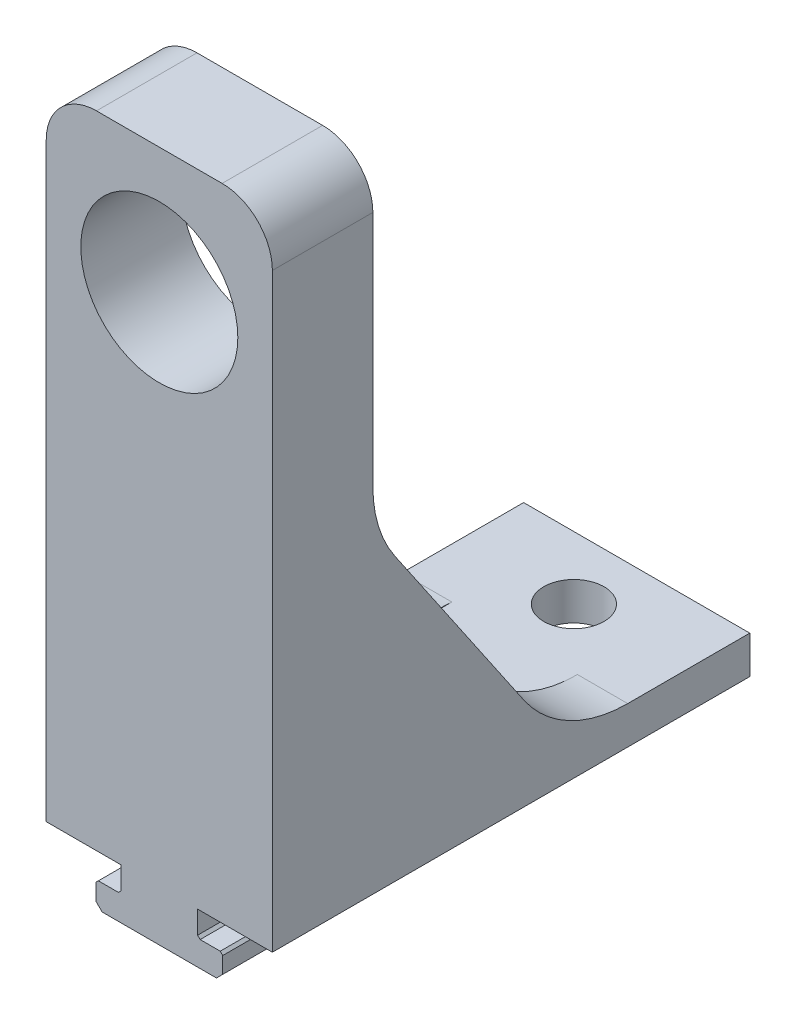
SolidWorks part; units mm, degrees
ref_plane "前视基准面" through (0, 0, 0) normal (0, 0, 1) x (1, 0, 0)
ref_plane "上视基准面" through (0, 0, 0) normal (0, 1, 0) x (1, 0, 0)
ref_plane "右视基准面" through (0, 0, 0) normal (1, 0, 0) x (0, 0, -1)
sketch "草图1" plane through (0, 0, 0) normal (0, 0, 1) x (1, 0, 0)
  line L0 (0, -1000) -> (0, 49000) construction
  line L1 (-3.2, 10) -> (-3.2, 8.5) construction
  line L2 (-10, -10) -> (10, -10) construction
  line L3 (-10, -10) -> (-10, 10) construction
  line L4 (-10, 10) -> (10, 10) construction
  line L5 (-1000, 0) -> (49000, 0) construction
  line L6 (10, -10) -> (10, 10) construction
  line L7 (-10, -10) -> (10, 10) construction
  line L8 (-10, 10) -> (10, -10) construction
  line L9 (-3.2, 8.5) -> (-5.5, 8.5) construction
  line L10 (-5.5, 8.5) -> (-5.5, 6.7) construction
  line L11 (-5.5, 6.7) -> (-2.8, 4) construction
  line L12 (-2.8, 4) -> (2.8, 4) construction
  line L13 (5.5, 6.7) -> (2.8, 4) construction
  line L14 (5.5, 8.5) -> (5.5, 6.7) construction
  line L15 (3.2, 8.5) -> (5.5, 8.5) construction
  line L16 (3.2, 10) -> (3.2, 8.5) construction
  line L17 (8.5, 3.2) -> (8.5, 5.5) construction
  line L18 (8.5, 5.5) -> (6.7, 5.5) construction
  line L19 (6.7, 5.5) -> (4, 2.8) construction
  line L20 (4, 2.8) -> (4, -2.8) construction
  line L21 (6.7, -5.5) -> (4, -2.8) construction
  line L22 (8.5, -5.5) -> (6.7, -5.5) construction
  line L23 (8.5, -3.2) -> (8.5, -5.5) construction
  line L24 (10, 3.2) -> (8.5, 3.2) construction
  line L25 (10, -3.2) -> (8.5, -3.2) construction
  line L26 (3.2, -8.5) -> (5.5, -8.5) construction
  line L27 (5.5, -8.5) -> (5.5, -6.7) construction
  line L28 (5.5, -6.7) -> (2.8, -4) construction
  line L29 (2.8, -4) -> (-2.8, -4) construction
  line L30 (-5.5, -6.7) -> (-2.8, -4) construction
  line L31 (-5.5, -8.5) -> (-5.5, -6.7) construction
  line L32 (-3.2, -8.5) -> (-5.5, -8.5) construction
  line L33 (3.2, -10) -> (3.2, -8.5) construction
  line L34 (-3.2, -10) -> (-3.2, -8.5) construction
  line L35 (-8.5, -3.2) -> (-8.5, -5.5) construction
  line L36 (-8.5, -5.5) -> (-6.7, -5.5) construction
  line L37 (-6.7, -5.5) -> (-4, -2.8) construction
  line L38 (-4, -2.8) -> (-4, 2.8) construction
  line L39 (-6.7, 5.5) -> (-4, 2.8) construction
  line L40 (-8.5, 5.5) -> (-6.7, 5.5) construction
  line L41 (-8.5, 3.2) -> (-8.5, 5.5) construction
  line L42 (-10, -3.2) -> (-8.5, -3.2) construction
  line L43 (-10, 3.2) -> (-8.5, 3.2) construction
  line L44 (-10, 10) -> (-50, 10) construction
  line L45 (-50, 10) -> (-50, -10) construction
  line L46 (-50, -10) -> (-10, -10) construction
  line L47 (-3.05, 10) -> (-9, 10)
  line L48 (-9, 10) -> (-9, 57)
  line L49 (-5, 61) -> (5, 61)
  line L50 (9, 57) -> (9, 10)
  line L51 (9, 10) -> (3.05, 10)
  line L52 (-9, 13) -> (9, 13)
  line L53 (-3.05, 10) -> (3.05, 10)
  line L68 (-24.55, 6) -> (-15.45, 6) construction
  line L70 (-3.05, 10) -> (-3.05, 8)
  line L71 (-3.05, 8) -> (-5.05, 8)
  line L72 (-5.05, 8) -> (-5.05, 6.5)
  line L73 (-5.05, 6.5) -> (-4.55, 6)
  line L74 (-4.55, 6) -> (4.55, 6)
  line L75 (5.05, 6.5) -> (4.55, 6)
  line L76 (5.05, 8) -> (5.05, 6.5)
  line L77 (3.05, 10) -> (3.05, 8)
  line L78 (3.05, 8) -> (5.05, 8)
  line L79 (-14.95, 6.5) -> (-15.45, 6) construction
  line L80 (-14.95, 8) -> (-14.95, 6.5) construction
  line L81 (-16.95, 8) -> (-14.95, 8) construction
  line L82 (-16.95, 10) -> (-16.95, 8) construction
  line L83 (-23.05, 10) -> (-23.05, 8) construction
  line L84 (-23.05, 8) -> (-25.05, 8) construction
  line L85 (-25.05, 8) -> (-25.05, 6.5) construction
  line L86 (-25.05, 6.5) -> (-24.55, 6) construction
  line L87 (-44.55, 6) -> (-35.45, 6) construction
  line L88 (-34.95, 6.5) -> (-35.45, 6) construction
  line L89 (-34.95, 8) -> (-34.95, 6.5) construction
  line L90 (-36.95, 8) -> (-34.95, 8) construction
  line L91 (-36.95, 10) -> (-36.95, 8) construction
  line L92 (-43.05, 10) -> (-43.05, 8) construction
  line L93 (-43.05, 8) -> (-45.05, 8) construction
  line L94 (-45.05, 8) -> (-45.05, 6.5) construction
  line L95 (-45.05, 6.5) -> (-44.55, 6) construction
  line L96 (-30, 10) -> (-30, -10) construction
  line L97 (-40, 10) -> (-40, -10) construction
  line L98 (-34, 4.55) -> (-34, -4.55) construction
  line L99 (-33.5, -5.05) -> (-34, -4.55) construction
  line L100 (-32, -5.05) -> (-33.5, -5.05) construction
  line L101 (-32, -3.05) -> (-32, -5.05) construction
  line L102 (-32, 3.05) -> (-28, 3.05) construction
  line L103 (-28, -3.05) -> (-32, -3.05) construction
  line L104 (-32, 3.05) -> (-32, 5.05) construction
  line L105 (-32, 5.05) -> (-33.5, 5.05) construction
  line L106 (-33.5, 5.05) -> (-34, 4.55) construction
  line L107 (-35.45, -6) -> (-44.55, -6) construction
  line L108 (-45.05, -6.5) -> (-44.55, -6) construction
  line L109 (-45.05, -8) -> (-45.05, -6.5) construction
  line L110 (-43.05, -8) -> (-45.05, -8) construction
  line L111 (-43.05, -10) -> (-43.05, -8) construction
  line L112 (-36.95, -10) -> (-36.95, -8) construction
  line L113 (-36.95, -8) -> (-34.95, -8) construction
  line L114 (-34.95, -8) -> (-34.95, -6.5) construction
  line L115 (-34.95, -6.5) -> (-35.45, -6) construction
  line L116 (-46, -4.55) -> (-46, 4.55) construction
  line L117 (-46.5, 5.05) -> (-46, 4.55) construction
  line L118 (-48, 5.05) -> (-46.5, 5.05) construction
  line L119 (-48, 3.05) -> (-48, 5.05) construction
  line L120 (-50, 3.05) -> (-48, 3.05) construction
  line L121 (-50, -3.05) -> (-48, -3.05) construction
  line L122 (-48, -3.05) -> (-48, -5.05) construction
  line L123 (-48, -5.05) -> (-46.5, -5.05) construction
  line L124 (-46.5, -5.05) -> (-46, -4.55) construction
  line L125 (-26.5, 5.05) -> (-26, 4.55) construction
  line L126 (-28, 5.05) -> (-26.5, 5.05) construction
  line L127 (-28, 3.05) -> (-28, 5.05) construction
  line L128 (-28, -3.05) -> (-28, -5.05) construction
  line L129 (-28, -5.05) -> (-26.5, -5.05) construction
  line L130 (-26.5, -5.05) -> (-26, -4.55) construction
  line L131 (-26, 4.55) -> (-26, -4.55) construction
  line L132 (-30, -3.05) -> (-32, -3.05) [skipped]
  line L133 (-30, 3.05) -> (-32, 3.05) [skipped]
  line L134 (-25.05, -6.5) -> (-24.55, -6) construction
  line L135 (-25.05, -8) -> (-25.05, -6.5) construction
  line L136 (-23.05, -8) -> (-25.05, -8) construction
  line L137 (-23.05, -10) -> (-23.05, -8) construction
  line L138 (-16.95, -10) -> (-16.95, -8) construction
  line L139 (-16.95, -8) -> (-14.95, -8) construction
  line L140 (-14.95, -8) -> (-14.95, -6.5) construction
  line L141 (-14.95, -6.5) -> (-15.45, -6) construction
  line L142 (-24.55, -6) -> (-15.45, -6) construction
  circle A0 centre (0, 51) radius 6.5 construction
  circle A1 centre (0, 51) radius 6.25
  circle A2 centre (0, 51) radius 2 construction
  arc A3 (5, 61) -> (9, 57) centre (5, 57) cw
  arc A4 (-9, 57) -> (-5, 61) centre (-5, 57) cw
  point P0 (0, 0)
  point P18 (0, 4)
  point P58 (0, 0)
  point P69 (9, 61)
  point P72 (-9, 61)
  point P110 (0, 6)
  point P154 (-40, 0)
  point P176 (-40, 0)
  point P188 (-40, 0)
  dimension "D12" = 13
  dimension "D17" = 4
  dimension "D10" = 4
  dimension "D11" = 12.5
  dimension "D1" = 20
  dimension "D2" = 20
  dimension "D3" = 6.4
  dimension "D4" = 1.5
  dimension "D5" = 11
  dimension "D6" = 6
  dimension "D7" = 1.8
  dimension "D9" = 60
  dimension "D13" = 41
  dimension "D14" = 3
  dimension "D15" = 10
  dimension "D16" = 3
  dimension "D26" = 3.05
  dimension "D27" = 2
  dimension "D28" = 2
  dimension "D29" = 1.5
  dimension "D30" = 2
  dimension "D31" = 4.55
  dimension "D33" = 10
  dimension "D8" = 18
  dimension "D18" = 4
extrude "凸台-拉伸1" add sketch "草图1" along normal blind 4 and the other way blind 4 contours L77 L78 L76 L75 L74 L73 L72 L71 L70 L82 L81 L80 L79 L68 L86 L85 L84 L83 L91 L90 L89 L88 L87 L95 L94 L93 L92 L111 L110 L109 L108 L107 L115 L114 L113 L112 L137 L136 L135 L134 L142 L141 L140 | L85 L86 L68 L79 L80 L81 L82 L83 L84 | L78 L77 L70 L71 L72 L73 L74 L75 L76 | L131 L125 L126 L127 L102 L104 L105 L106 L98 L99 L100 L101 L103 L128 L129 L130 | L94 L95 L87 L88 L89 L90 L91 L92 L93 | L114 L115 L107 L108 L109 L110 L111 L112 L113 | L142 L134 L135 L136 L137 L138 L139 L140 L141 | A4 L48 L52 L50 A3 L49 A1 | L47 L53 L51 L50 L52 L48 region at (0, 11.5, 0) region at (0, 7.7654, 0) region at (0, 34.4446, 0)
extrude "凸台-拉伸2" add sketch "草图1<6>" against normal blind 34 contours L47 L53 L51 L50 L52 L48 region at (0, 11.5, 0)
sketch "草图1<6>" plane through (0, 0, 0) normal (0, 0, 1) x (1, 0, 0) same geometry as "草图1"
sketch "草图2" plane through (9, 0, 0) normal (1, 0, 0) x (0, 0, -1)
  line L0 (4, 35) -> (19, 13)
  line L1 (4, 57) -> (4, 13) construction
  line L2 (34, 13) -> (4, 13) construction
rib "筋1" sketch "草图2" sketch "草图2" thickness 4 extrusion direction parallel to sketch draft on no parameters "D1"=4
mirror "镜向1" about plane through (0, 0, 0) normal (1, 0, 0) of "筋1"
fillet "圆角1" radius 10 4 edges at (7, 13, -19) (-7, 13, -19) (-7, 35, -4) (7, 35, -4)
extrude "凸台-拉伸3" add sketch "草图1<7>" against normal offset from surface (22 mm away) 12 contours L78 L77 L53 L70 L71 L72 L73 L74 L75 L76 region at (0, 7.7654, 0) up to face at (0, 11.5, -34)
sketch "草图1<7>" plane through (0, 0, 0) normal (0, 0, 1) x (1, 0, 0) same geometry as "草图1"
chamfer "倒角1" distance 0.2 angle 45 4 edges at (-5.05, 8, -9) (-3.05, 8, -9) (5.05, 8, -9) (3.05, 8, -9)
sketch "草图4" plane through (0, 13, 0) normal (0, 1, 0) x (1, 0, 0)
  line L0 (-9, 34) -> (9, 34) construction
  circle A0 centre (0, 29) radius 2.4
  point P2 (0, 34)
  dimension "D1" = 4.8
  dimension "D2" = 5
extrude "切除-拉伸1" cut sketch "草图4" against normal through all
